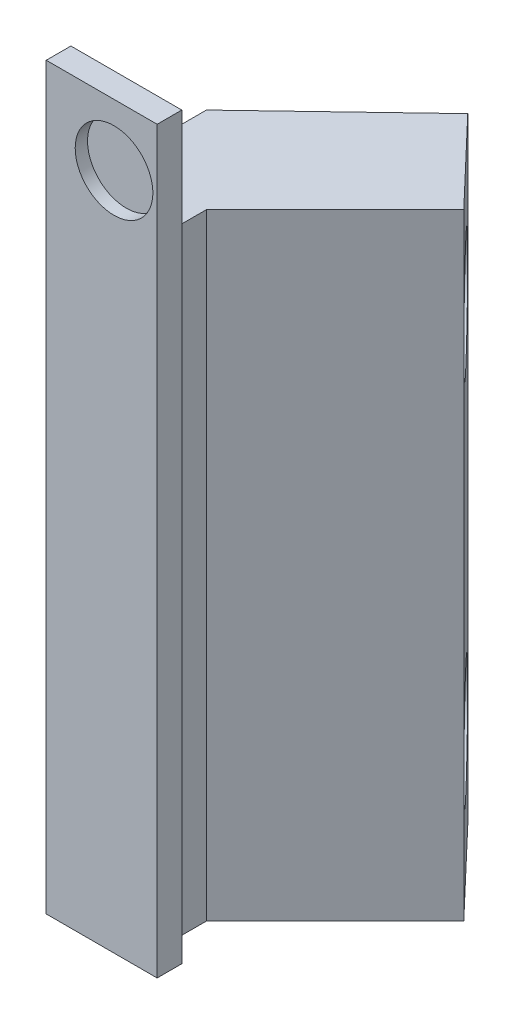
SolidWorks part; units mm, degrees
ref_plane "Front" through (0, 0, 0) normal (0, 0, 1) x (1, 0, 0)
ref_plane "Top" through (0, 0, 0) normal (0, 1, 0) x (1, 0, 0)
ref_plane "Right" through (0, 0, 0) normal (1, 0, 0) x (0, 0, -1)
other "Configuration Table"
sketch "Sketch1" plane through (0, 0, 0) normal (0, 1, 0) x (1, 0, 0)
  line L0 (0, 0) -> (0, -6)
  line L1 (0, -6) -> (9, -6)
  line L2 (9, -6) -> (9, -4)
  line L3 (9, -4) -> (2, -4)
  line L4 (0, 0) -> (7, 0)
  line L5 (7, 0) -> (7, -2)
  line L6 (7, -2) -> (2, -2)
  line L7 (2, -2) -> (2, -4)
  dimension "D1" = 6
  dimension "D2" = 9
  dimension "D3" = 2
  dimension "D4" = 2
  dimension "D5" = 5
  dimension "D6" = 7
extrude "Boss-Extrude1" add sketch "Sketch1" along normal blind 50
sketch "Sketch2" plane through (0, 50, 0) normal (0, 1, 0) x (1, 0, 0)
  line L1 (7, -2) -> (0, -2)
  line L2 (7, -2) -> (7, 0)
  line L3 (7, 0) -> (0, 0)
  line L4 (0, -2) -> (0, 0)
  line L5 (0, -6) -> (9, -6)
  line L6 (0, -6) -> (0, -4)
  line L7 (0, -4) -> (9, -4)
  line L8 (9, -6) -> (9, -4)
  line M2 (0, 0) -> (0, -6)
  line M3 (0, -6) -> (9, -6)
  line M4 (9, -6) -> (9, -4)
  line M5 (9, -4) -> (2, -4)
  dimension "D1" = 9
extrude "Boss-Extrude2" add sketch "Sketch2" along normal blind 10 contours L7 M2 M3 M4 M5 | L5 L8 L7 M4 region at (4.5, 50, 5)
sketch "Sketch3" plane through (0, 0, 6) normal (0, 0, -1) x (-1, 0, 0)
  line L0 (0, 50) -> (0, 0) construction
  line L2 (0, 60) -> (-9, 60) construction
  circle A0 centre (-5.5, 55) radius 3.15
  dimension "D1" = 6.3
  dimension "D2" = 5.5
  dimension "D3" = 5
extrude "Cut-Extrude1" cut sketch "Sketch3" along normal blind 1
sketch "Sketch4" plane through (0, 0, 0) normal (0, -1, 0) x (1, 0, 0)
  line L0 (7, 6) -> (0, 13)
  line L1 (0, 13) -> (0, 6)
  line L2 (0, 6) -> (9, 6) construction
  line L3 (0, 13) -> (10.8579, 23.3492)
  line L4 (10.8579, 23.3492) -> (17.4417, 16.4417)
  line L5 (17.4417, 16.4417) -> (7, 6)
  line L6 (0, 3) -> (30, 3) construction
  line L7 (0, 0) -> (0, 6) construction
  line L8 (10.8579, -17.3492) -> (17.4417, -10.4417)
  line L9 (17.4417, -10.4417) -> (7, 0)
  line L10 (0, -7) -> (0, 0)
  line L11 (7, 0) -> (0, -7)
  line L12 (0, -7) -> (10.8579, -17.3492)
  line M2 (0, 0) -> (7, 0)
  dimension "D1" = 7
  dimension "D2" = 15
  dimension "D3" = 30
  dimension "D4" = 7
extrude "Boss-Extrude3" add sketch "Sketch4" against normal blind 50 contours L11 L12 L8 L9 | L11 L10 M2 region at (8.7835, 0, -8.675) region at (2.3333, 0, -2.3333)
sketch "Sketch5" plane through (0, 0, 0) normal (0, -1, 0) x (1, 0, 0)
  line L0 (7, 2) -> (7, 0) construction
  line L1 (2, 4) -> (7, 4)
  line L2 (2, 4) -> (2, 2)
  line L3 (2, 2) -> (7, 2)
  line L4 (7, 4) -> (7, 2)
  line L5 (2, 2) -> (7, 2) construction
extrude "Boss-Extrude4" add sketch "Sketch5" against normal blind 1
sketch "Sketch6" plane through (14.3539, 0, -13.6813) normal (0.7239, 0, -0.6899) x (-0.6899, 0, -0.7239)
  line L0 (0.2958, 50) -> (0.2958, 0) construction
  line L1 (5.067, 50) -> (-4.4755, 50) construction
  line L2 (5.067, 0) -> (-4.4755, 0) construction
  circle A0 centre (0.2958, 40) radius 2.5
  circle A1 centre (0.2958, 40) radius 4.5
  circle A2 centre (0.2958, 10) radius 2.5
  circle A3 centre (0.2958, 10) radius 4.5
  dimension "D1" = 5
  dimension "D2" = 9
  dimension "D3" = 5
  dimension "D4" = 9
  dimension "D5" = 10
  dimension "D6" = 10
extrude "Cut-Extrude2" cut sketch "Sketch6" against normal through all contours L0 A0 | A0 L0 | L0 A2 | A2 L0 region at (13.4178, 40, -14.6635) region at (14.8819, 40, -13.1274) region at (13.4178, 10, -14.6635) region at (14.8819, 10, -13.1274)
extrude "Cut-Extrude3" cut sketch "Sketch6<3>" against normal blind 1 contours L0 A1 A0 | A1 L0 A0 | L0 A3 A2 | A3 L0 A2 region at (12.0035, 43.1108, -16.1473) region at (12.0035, 13.1108, -16.1473) region at (14.2193, 13.5, -13.8226) region at (14.2193, 43.5, -13.8226)
sketch "Sketch6<3>" plane through (14.3539, 0, -13.6813) normal (0.7239, 0, -0.6899) x (-0.6899, 0, -0.7239) same geometry as "Sketch6"
